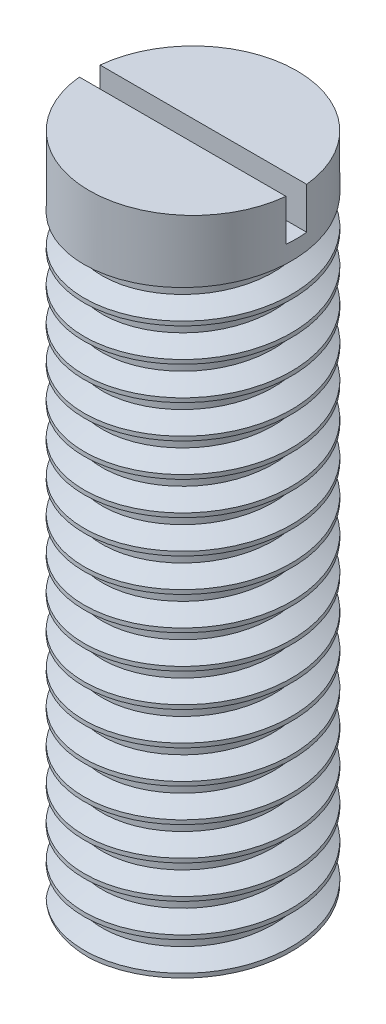
SolidWorks part; units mm, degrees
ref_plane "Front Plane" through (0, 0, 0) normal (0, 0, 1) x (1, 0, 0)
ref_plane "Top Plane" through (0, 0, 0) normal (0, 1, 0) x (1, 0, 0)
ref_plane "Right Plane" through (0, 0, 0) normal (1, 0, 0) x (0, 0, -1)
sketch "Sketch1" plane through (0, 0, 0) normal (0, 1, 0) x (1, 0, 0)
  circle A0 centre (0, 0) radius 2.5
extrude "Boss-Extrude1" add sketch "Sketch1" along normal blind 15
thread "Thread1" pitch 0.8 method cut profile "Thread Profile1" start angle 0, offset 0, length 15, pitch 0.8, diameter 5
ref_plane "Plane1" through (-2.5, 15, 0) normal (0, 0, 1) x (-1, 0, 0)
sketch "Thread Profile1" plane through (-2.5, 15, 0) normal (0, 0, 1) x (-1, 0, 0)
  line L0 (0, 0) -> (0, 0.8) construction
  line L11 (0, 0) -> (0, 0.7)
  line L12 (0, 0.7) -> (-0.433, 0.45)
  line L13 (-0.433, 0.45) -> (-0.433, 0.25)
  line L15 (-0.433, 0.25) -> (0, 0)
  line L17 (-0.433, 0.35) -> (0, 0.35) construction
  point P2 (0, 0)
  dimension "Pitch" = 0.8
  dimension "Profile_Angle" = 60
  dimension "Profile_Land" = 0.2
  dimension "Profile_Height" = 0.433
sketch "Sketch4" plane through (0, 15, 0) normal (0, 1, 0) x (1, 0, 0)
  line L1 (-2.5, 0.25) -> (-2.5, -0.25)
  line L2 (2.5, 0.25) -> (2.5, -0.25)
  line L3 (-2.5, -0.25) -> (2.5, -0.25)
  line L4 (-2.5, 0.25) -> (2.5, 0.25)
  circle A1 centre (0, 0) radius 2.5
  circle M6 centre (0, 0) radius 2.5
extrude "Boss-Extrude2" add sketch "Sketch4" along normal blind 1 contours L4 M6 | L3 M6 region at (0, 15, -1.1974) region at (0, 15, 1.1974)
